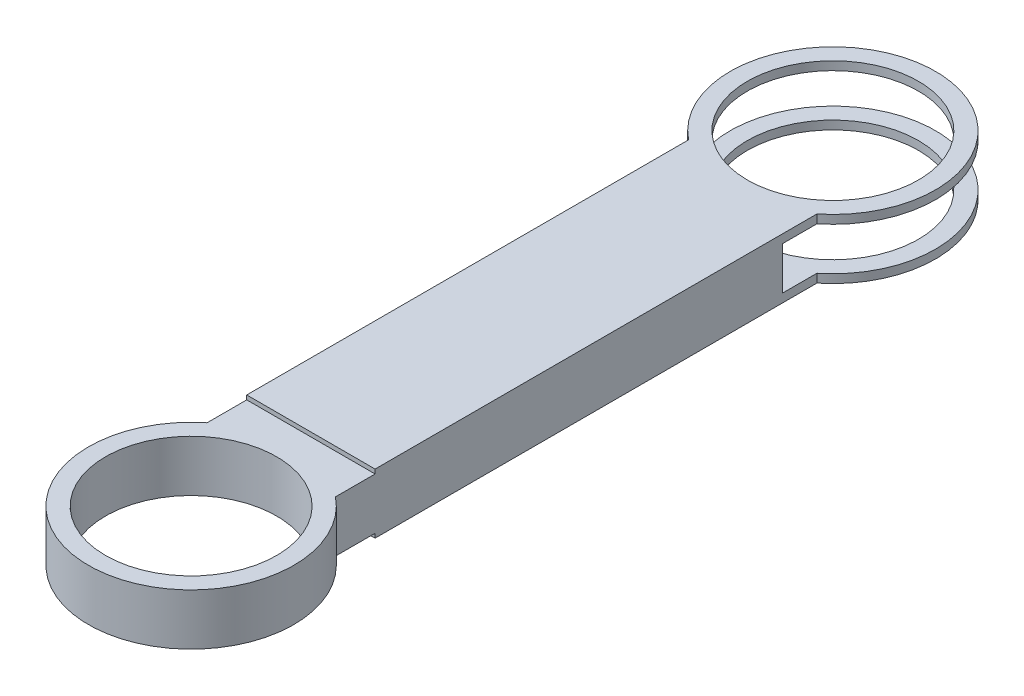
SolidWorks part; units mm, degrees
ref_plane "Front Plane" through (0, 0, 0) normal (0, 0, 1) x (1, 0, 0)
ref_plane "Top Plane" through (0, 0, 0) normal (0, 1, 0) x (1, 0, 0)
ref_plane "Right Plane" through (0, 0, 0) normal (1, 0, 0) x (0, 0, -1)
sketch "Profile Sketch" plane through (0, 0, 0) normal (0, 1, 0) x (1, 0, 0)
  line L0 (-7.5, 28.1325) -> (-7.5, -28.1325)
  line L1 (7.5, 28.1325) -> (7.5, -28.1325)
  line L2 (-7.5, 0) -> (7.5, 0) construction
  circle A0 centre (0, -37.5) radius 10
  circle A1 centre (0, 37.5) radius 10
  arc A2 (7.5, 28.1325) -> (-7.5, 28.1325) centre (0, 37.5) ccw
  arc A3 (-7.5, -28.1325) -> (7.5, -28.1325) centre (0, -37.5) ccw
  point P9 (-7.5, 0)
  point P12 (7.5, 0)
  point P13 (0, 0)
  dimension "D1" = 20
  dimension "D2" = 2
  dimension "D3" = 75
  dimension "D4" = 15
extrude "Profile Extrude" add sketch "Profile Sketch" along normal blind 7
sketch "Wrist Cut Sketch" plane through (0, 0, 0) normal (0, 1, 0) x (1, 0, 0)
  line L0 (-7.5, -28.1325) -> (-7.5, -23.5)
  line L1 (-7.5, -23.5) -> (7.5, -23.5)
  line L2 (7.5, -23.5) -> (7.5, -28.1325)
  line L3 (7.5, -28.1325) -> (7.5, 28.1325) construction
  line L4 (-7.5, 28.1325) -> (-7.5, -28.1325) construction
  arc A0 (-7.5, -28.1325) -> (7.5, -28.1325) centre (0, -37.5) ccw
  arc A1 (-7.5, -28.1325) -> (7.5, -28.1325) centre (0, -37.5) ccw construction
  circle A2 centre (0, -37.5) radius 10 construction
  dimension "D1" = 14
extrude "Upper Wrist Cut" cut sketch "Wrist Cut Sketch" along normal blind 0.5 from surface starting at face at (0, 0, 0)
extrude "Lower Wrist Cut" cut sketch "Sketch2<2>" against normal blind 0.5 from surface starting at face at (0, 7, 47.5)
sketch "Sketch2<2>" plane through (0, 0, 0) normal (0, 1, 0) x (1, 0, 0) same geometry as "Wrist Cut Sketch"
sketch "Finger Cut Sketch" plane through (0, 0, 0) normal (1, 0, 0) x (0, 0, -1)
  line L1 (49.5, 1) -> (24.1325, 1)
  line L2 (49.5, 1) -> (49.5, 6)
  line L3 (49.5, 6) -> (24.1325, 6)
  line L4 (24.1325, 1) -> (24.1325, 6)
  line L5 (49.5, 1) -> (24.1325, 6) construction
  line L6 (49.5, 6) -> (24.1325, 1) construction
  line L8 (49.5, 0) -> (49.5, 7) construction
  line L9 (28.1325, 7) -> (28.1325, 0) construction
  line L10 (49.5, 7) -> (28.1325, 7) construction
  line L11 (28.1325, 0) -> (49.5, 0) construction
  point P0 (36.8163, 3.5)
  dimension "D1" = 4
  dimension "D2" = 1
  dimension "D3" = 1
extrude "Finger Cut" cut sketch "Finger Cut Sketch" against normal up to surface and the other way up to surface up to face at (0, 3.5, -38.8163) other way up to face at (0, 3.5, -38.8163)
sketch "Sketch1" plane through (7.5, 0, 0) normal (1, 0, 0) x (0, 0, -1)
  line L0 (28.1325, 6) -> (28.1325, 1) construction
  line L1 (28.1325, 1) -> (24.1325, 1)
  line L2 (28.1325, 1) -> (28.1325, 6)
  line L3 (28.1325, 6) -> (24.1325, 6)
  line L4 (24.1325, 1) -> (24.1325, 6)
  line L5 (28.1325, 1) -> (24.1325, 6) construction
  line L6 (28.1325, 6) -> (24.1325, 1) construction
  line L9 (49.5, 1) -> (28.1325, 1) construction
  line L10 (28.1325, 6) -> (49.5, 6) construction
  point P0 (26.1325, 3.5)
  dimension "D1" = 4
extrude "Cut-Extrude2" cut sketch "Sketch1" against normal up to surface (15 mm away) up to face at (-7.5, 3.5, 3.7735)
